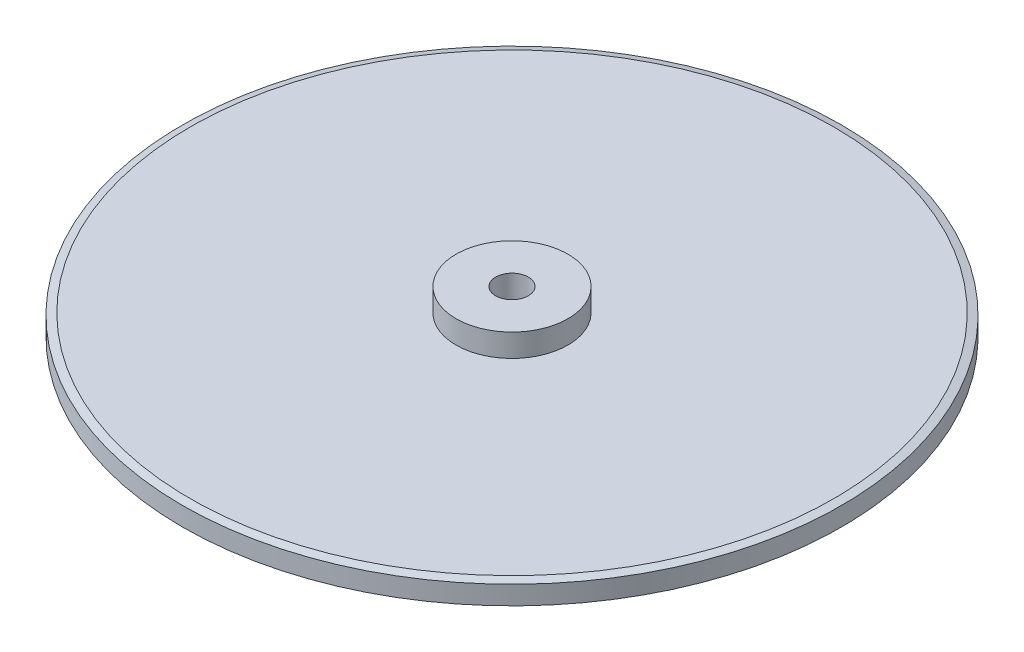
SolidWorks part; units mm, degrees
material "Сталь ШХ15 ГОСТ 801-78"
ref_plane "Plane1" through (0, 0, 0) normal (0, 0, 1) x (1, 0, 0)
ref_plane "Plane2" through (0, 0, 0) normal (0, 1, 0) x (1, 0, 0)
ref_plane "Plane3" through (0, 0, 0) normal (1, 0, 0) x (0, 0, -1)
sketch "Эскиз1" plane through (0, 0, 0) normal (0, 0, 1) x (1, 0, 0)
  line L0 (0, 0) -> (70.7, 0)
  line L1 (70.7, 0) -> (70.7, 4.9)
  line L2 (70.7, 4.9) -> (12, 4.9)
  line L3 (12, 4.9) -> (12, 9.8)
  line L4 (12, 9.8) -> (0, 9.8)
  line L5 (0, 9.8) -> (0, 0)
  dimension "D1" = 4.9
  dimension "30" = 70.7
  dimension "D3" = 12
  dimension "D4" = 4.9
ref_axis "Ось1" through (0, 9.8, 0) along (0, -1, 0)
revolve "Повернуть2" add sketch "Эскиз1" angle 360 about axis through (0, 9.8, 0) along (0, -1, 0)
chamfer "Фаска1" distance 1.645 angle 15 1 edges at (0, 4.9, 70.7) first distance on face at (0, 4.9, 12)
chamfer "Фаска2" distance 1.645 angle 15 1 edges at (0, 0, 70.7) first distance on face at (0, 0, 70.7)
sketch "Эскиз2" plane through (0, 0, 0) normal (0, -1, 0) x (-1, 0, 0)
  circle A0 centre (0, 0) radius 3.5
  dimension "D1" = 7
sketch "Эскиз3" plane through (0, 0, 0) normal (0, 0, 1) x (1, 0, 0)
  circle A0 centre (0, 5.828) radius 1
extrude "Вырез-Вытянуть3" cut sketch "Эскиз2" against normal through all both contours A0
